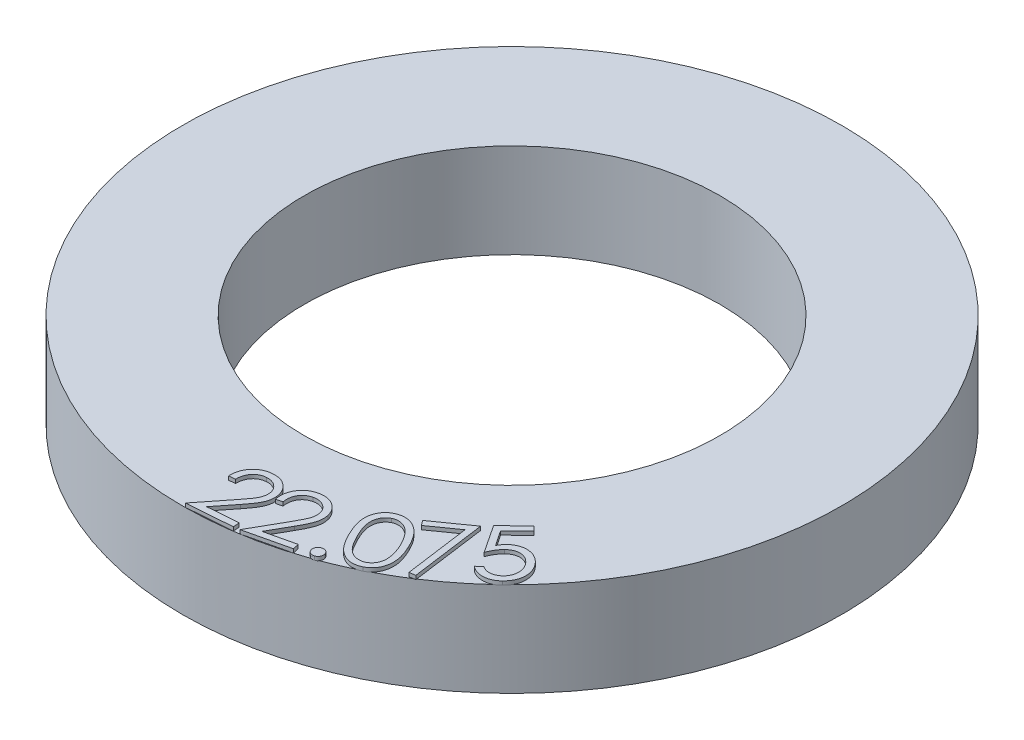
SolidWorks part; units mm, degrees
ref_plane "Front Plane" through (0, 0, 0) normal (0, 0, 1) x (1, 0, 0)
ref_plane "Top Plane" through (0, 0, 0) normal (0, 1, 0) x (1, 0, 0)
ref_plane "Right Plane" through (0, 0, 0) normal (1, 0, 0) x (0, 0, -1)
ref_axis "X" through (-88.99, 0, 0) along (1, 0, 0)
ref_axis "Y" through (0, 55, 0) along (0, -1, 0)
ref_axis "Z" through (0, 0, -88.99) along (0, 0, 1)
sketch "Sketch1" plane through (0, 0, 0) normal (0, 1, 0) x (1, 0, 0)
  circle A0 centre (0, 0) radius 17.5
  circle A1 centre (0, 0) radius 11.0375
  dimension "D1" = 35
  dimension "D2" = 22.075
extrude "Boss-Extrude1" add sketch "Sketch1" along normal blind 5
sketch "Sketch4" plane through (0, 5, 0) normal (0, 1, 0) x (1, 0, 0)
  text T0 "22.075"
extrude "Boss-Extrude4" add sketch "Sketch4" along normal blind 0.2
